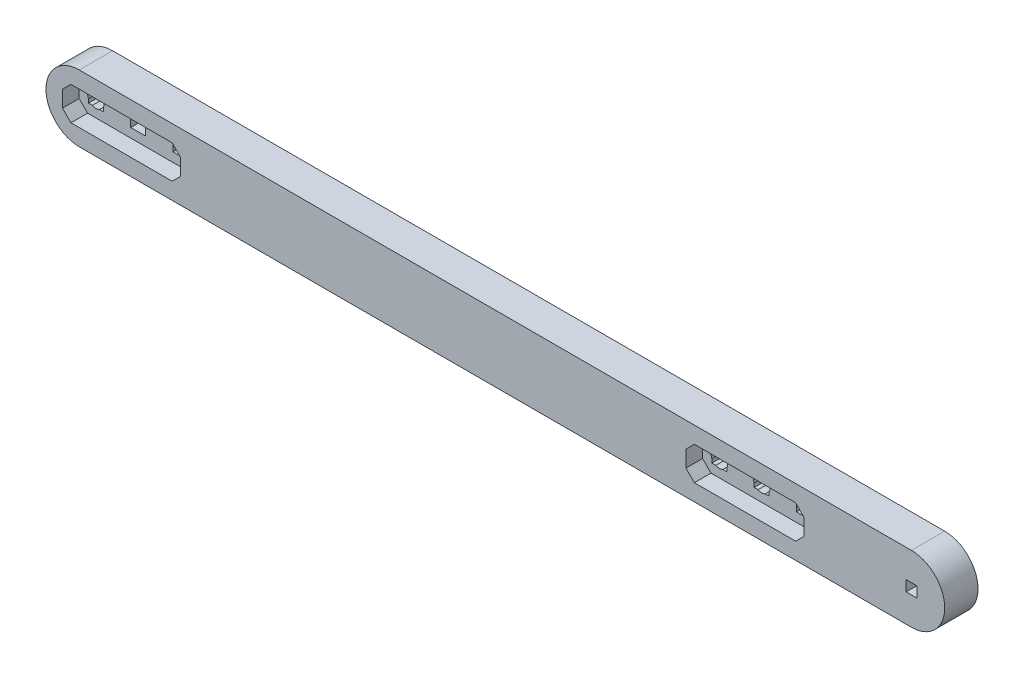
SolidWorks part; units mm, degrees
ref_plane "Front Plane" through (0, 0, 0) normal (0, 0, 1) x (1, 0, 0)
ref_plane "Top Plane" through (0, 0, 0) normal (0, 1, 0) x (1, 0, 0)
ref_plane "Right Plane" through (0, 0, 0) normal (1, 0, 0) x (0, 0, -1)
sketch "Sketch1" plane through (0, 0, 0) normal (0, 0, 1) x (1, 0, 0)
  line L0 (50, 10) -> (-200, 10)
  line L1 (50, -10) -> (-200, -10)
  line L3 (48.4, -1.6) -> (51.6, -1.6)
  line L4 (48.4, -1.6) -> (48.4, 1.6)
  line L5 (48.4, 1.6) -> (51.6, 1.6)
  line L6 (51.6, -1.6) -> (51.6, 1.6)
  line L7 (48.4, -1.6) -> (51.6, 1.6) construction
  line L8 (48.4, 1.6) -> (51.6, -1.6) construction
  circle A0 centre (0, 0) radius 2.5
  circle A2 centre (-200, 0) radius 2.5
  arc A3 (-200, 10) -> (-200, -10) centre (-200, 0) ccw
  arc A4 (50, 10) -> (50, -10) centre (50, 0) cw
  point P12 (50, 0)
  dimension "D1" = 5
  dimension "D4" = 10
  dimension "D5" = 10
  dimension "D2" = 50
  dimension "D3" = 200
  dimension "D6" = 3.2
extrude "Boss-Extrude1" add sketch "Sketch1" along normal blind 10
sketch "Sketch2" plane through (0, 0, 10) normal (0, 0, 1) x (1, 0, 0)
  line L0 (15.21, -5) -> (17.75, -2.46)
  line L1 (17.75, -2.46) -> (17.75, 2.46)
  line L2 (15.21, -5) -> (-15.21, -5)
  line L3 (-17.75, -2.46) -> (-17.75, 2.46)
  line L4 (15.21, 5) -> (-15.21, 5)
  line L5 (17.75, -5) -> (-17.75, 5) construction
  line L6 (-17.75, -5) -> (17.75, 5) construction
  line L7 (17.75, 2.46) -> (15.21, 5)
  line L8 (-17.75, 2.46) -> (-15.21, 5)
  line L9 (-15.21, -5) -> (-17.75, -2.46)
  line L10 (14.95, 2.25) -> (10.45, 2.25)
  line L11 (14.95, 2.25) -> (14.95, -2.25)
  line L12 (14.95, -2.25) -> (10.45, -2.25)
  line L13 (10.45, 2.25) -> (10.45, -2.25)
  line L14 (14.95, 2.25) -> (10.45, -2.25) construction
  line L15 (14.95, -2.25) -> (10.45, 2.25) construction
  line L16 (2.25, 2.25) -> (-2.25, 2.25)
  line L17 (2.25, 2.25) -> (2.25, -2.25)
  line L18 (2.25, -2.25) -> (-2.25, -2.25)
  line L19 (-2.25, 2.25) -> (-2.25, -2.25)
  line L20 (2.25, 2.25) -> (-2.25, -2.25) construction
  line L21 (2.25, -2.25) -> (-2.25, 2.25) construction
  line L22 (-10.45, 2.25) -> (-14.95, 2.25)
  line L23 (-10.45, 2.25) -> (-10.45, -2.25)
  line L24 (-10.45, -2.25) -> (-14.95, -2.25)
  line L25 (-14.95, 2.25) -> (-14.95, -2.25)
  line L26 (-10.45, 2.25) -> (-14.95, -2.25) construction
  line L27 (-10.45, -2.25) -> (-14.95, 2.25) construction
  line L28 (-172.09, -5) -> (-169.55, -2.46)
  line L29 (-169.55, -2.46) -> (-169.55, 2.46)
  line L30 (-172.09, -5) -> (-202.51, -5)
  line L31 (-205.05, -2.46) -> (-205.05, 2.46)
  line L32 (-172.09, 5) -> (-202.51, 5)
  line L33 (-169.55, -5) -> (-205.05, 5) construction
  line L34 (-205.05, -5) -> (-169.55, 5) construction
  line L35 (-169.55, 2.46) -> (-172.09, 5)
  line L36 (-205.05, 2.46) -> (-202.51, 5)
  line L37 (-202.51, -5) -> (-205.05, -2.46)
  line L38 (-172.35, 2.25) -> (-176.85, 2.25)
  line L39 (-172.35, 2.25) -> (-172.35, -2.25)
  line L40 (-172.35, -2.25) -> (-176.85, -2.25)
  line L41 (-176.85, 2.25) -> (-176.85, -2.25)
  line L42 (-172.35, 2.25) -> (-176.85, -2.25) construction
  line L43 (-172.35, -2.25) -> (-176.85, 2.25) construction
  line L44 (-185.05, 2.25) -> (-189.55, 2.25)
  line L45 (-185.05, 2.25) -> (-185.05, -2.25)
  line L46 (-185.05, -2.25) -> (-189.55, -2.25)
  line L47 (-189.55, 2.25) -> (-189.55, -2.25)
  line L48 (-185.05, 2.25) -> (-189.55, -2.25) construction
  line L49 (-185.05, -2.25) -> (-189.55, 2.25) construction
  line L50 (-197.75, 2.25) -> (-202.25, 2.25)
  line L51 (-197.75, 2.25) -> (-197.75, -2.25)
  line L52 (-197.75, -2.25) -> (-202.25, -2.25)
  line L53 (-202.25, 2.25) -> (-202.25, -2.25)
  line L54 (-197.75, 2.25) -> (-202.25, -2.25) construction
  line L55 (-197.75, -2.25) -> (-202.25, 2.25) construction
  circle A0 centre (-12.7, 0) radius 2.5
  circle A1 centre (-200, 0) radius 2.5
  circle A2 centre (-200, 0) radius 2.5 construction
  point P0 (12.7, 0)
  point P2 (0, 0)
  point P18 (0, 0)
  point P23 (-12.7, 0)
  point P30 (0, 0)
  point P32 (18.2895, -5.9071)
  point P33 (-174.6, 0)
  point P35 (-187.3, 0)
  point P51 (-187.3, 0)
  point P56 (-200, 0)
  point P63 (-186.1023, 0)
  point P64 (-192.4303, -0.1817)
  point P67 (0, 0)
  circle M22 centre (0, 0) radius 2.5
  circle M24 centre (-200, 0) radius 2.5
  dimension "D12" = 5
  dimension "D26" = 5
  dimension "D1" = 2.54
  dimension "D2" = 2.54
  dimension "D3" = 2.54
  dimension "D4" = 2.54
  dimension "D5" = 2.54
  dimension "D6" = 2.54
  dimension "D7" = 2.54
  dimension "D8" = 2.54
  dimension "D9" = 12.7
  dimension "D10" = 12.7
  dimension "D11" = 4.5
  dimension "D13" = 10
  dimension "D14" = 35.5
  dimension "D15" = 2.54
  dimension "D16" = 2.54
  dimension "D17" = 2.54
  dimension "D18" = 2.54
  dimension "D19" = 2.54
  dimension "D20" = 2.54
  dimension "D21" = 2.54
  dimension "D22" = 2.54
  dimension "D23" = 12.7
  dimension "D24" = 12.7
  dimension "D25" = 4.5
  dimension "D27" = 10
  dimension "D28" = 35.5
extrude "Cut-Extrude2" cut sketch "Sketch2<3>" against normal through all contours L23 A0 L22 L25 L24 | L25 L24 L23 L22 | A0 | L16 L19 L18 L17 | L10 L13 L12 L11 | L53 L52 L51 L50 | A1 | L44 L47 L46 L45 | L38 L41 L40 L39 region at (-12.7, 0, 10)
sketch "Sketch2<3>" plane through (0, 0, 10) normal (0, 0, 1) x (1, 0, 0) same geometry as "Sketch2"
extrude "Cut-Extrude1" cut sketch "Sketch2" against normal blind 5 contours L9 L2 L0 L1 L7 L4 L8 L3 A0 L22 L23 L24 L25 L19 L16 L17 L18 L13 L10 L11 L12 M22 | L37 L30 L28 L29 L35 L32 L36 L31 L53 L50 L51 L52 L47 L44 L45 L46 L41 L38 L39 L40 M24 region at (0, -4.6312, 10) region at (-187.3, -4.6312, 10)
